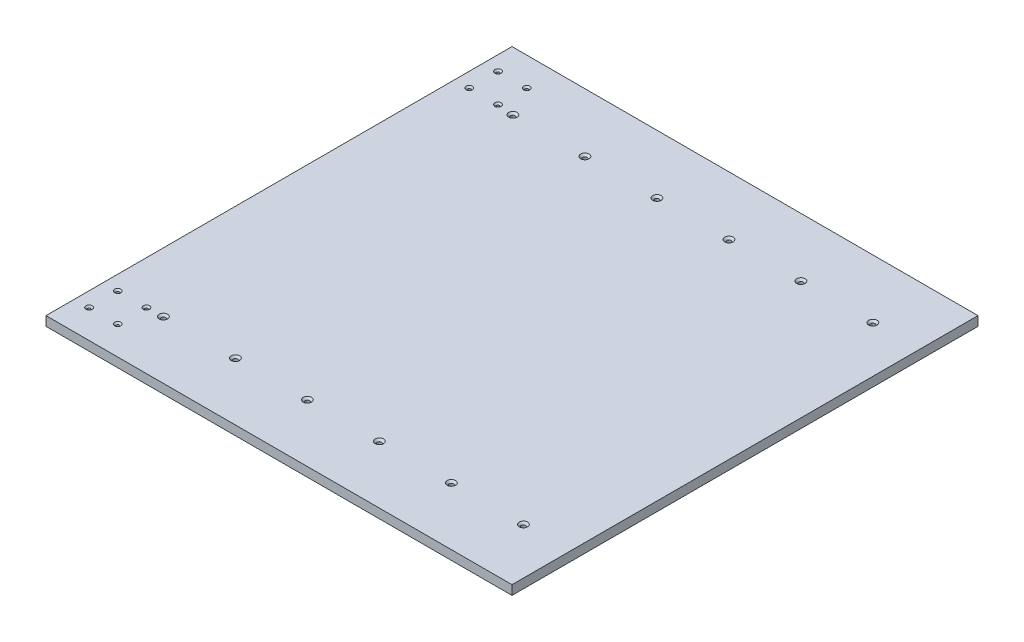
SolidWorks part; units mm, degrees
material "Buk"
ref_plane "Płaszczyzna przednia" through (0, 0, 0) normal (0, 0, 1) x (1, 0, 0)
ref_plane "Płaszczyzna górna" through (0, 0, 0) normal (0, 1, 0) x (1, 0, 0)
ref_plane "Płaszczyzna prawa" through (0, 0, 0) normal (1, 0, 0) x (0, 0, -1)
sketch "Szkic1" plane through (0, 0, 0) normal (0, 1, 0) x (1, 0, 0)
  line L1 (0, 0) -> (500, 0)
  line L2 (0, 0) -> (0, 500)
  line L3 (0, 500) -> (500, 500)
  line L4 (500, 0) -> (500, 500)
  dimension "D1" = 500
extrude "Dodanie-wyciągnięcie1" add sketch "Szkic1" along normal blind 10
sketch "Szkic2" plane through (0, 10, 0) normal (0, 1, 0) x (1, 0, 0)
  line L0 (0, 0) -> (500, 0) construction
  line L1 (0, 500) -> (0, 0) construction
  line L2 (0, 250) -> (500, 250) construction
  line L3 (500, 0) -> (500, 500) construction
  circle A0 centre (15.6, 30.6) radius 1.6
  circle A1 centre (15.6, 61.4) radius 1.6
  circle A2 centre (46.4, 61.4) radius 1.6
  circle A3 centre (46.4, 30.6) radius 1.6
  circle A4 centre (15.6, 438.6) radius 1.6
  circle A5 centre (15.6, 469.4) radius 1.6
  circle A6 centre (46.4, 469.4) radius 1.6
  circle A7 centre (46.4, 438.6) radius 1.6
  dimension "D1" = 3.2
  dimension "D2" = 3.2
  dimension "D3" = 3.2
  dimension "D4" = 3.2
  dimension "D5" = 30.6
  dimension "D6" = 30.6
  dimension "D7" = 30.8
  dimension "D8" = 15.6
  dimension "D9" = 15.6
  dimension "D10" = 30.8
  dimension "D11" = 30.8
  dimension "D12" = 30.8
hole_wizard "Pogłębienie stożkowe pod M3 Wkręt ustalający1" positions "Szkic3" profile "Szkic5" countersink size "M3" standard "Ansi Metric"
sketch "Szkic3" plane through (0, 10, 0) normal (0, 1, 0) x (1, 0, 0)
  point P0 (46.4, 30.6)
  point P3 (46.4, 61.4)
  point P6 (15.6, 61.4)
  point P9 (15.6, 30.6)
  point P12 (46.4, 438.6)
  point P15 (46.4, 469.4)
  point P18 (15.6, 469.4)
  point P21 (15.6, 438.6)
sketch "Szkic5" plane through (46.4, 10, -30.6) normal (1, 0, 0) x (0, 0, 1)
  line L0 (0, 0) -> (0, 11.0215)
  line L1 (0, 11.0215) -> (1.7, 10)
  line L2 (1.7, 10) -> (1.7, 1.66)
  line L3 (1.7, 1.66) -> (3.36, 0)
  line L5 (3.36, 0) -> (0, 0)
  line L6 (-1.7, 1.66) -> (-3.36, 0) construction
  line L10 (0, 11.0215) -> (-1.7, 10) construction
  line L11 (0, -6.35) -> (0, 107.95) construction
  dimension "Œrednica otworu" = 3.4
  dimension "G³êbokoœc otworu" = 10
  dimension "Œrednica zewnêtrznego pog³êbienia sto¿kowego" = 6.72
  dimension "K¹t zewnêtrznego pog³êbienia sto¿kowego" = 90
  dimension "K¹t wiert³a" = 118
hole_wizard "Pogłębienie stożkowe pod M4 Wkręt ustalający1" positions "Szkic6" profile "Szkic7" countersink size "M4" standard "Ansi Metric"
sketch "Szkic6" plane through (0, 10, 0) normal (0, 1, 0) x (1, 0, 0)
  line L0 (0, 500) -> (0, 0) construction
  line L1 (0, 0) -> (500, 0) construction
  point P0 (63.9, 62.07)
  point P14 (141.15, 62.07)
  point P15 (218.4, 62.07)
  point P16 (295.65, 62.07)
  point P17 (372.9, 62.07)
  point P18 (450.15, 62.07)
  point P19 (141.15, 437.07)
  point P20 (218.4, 437.07)
  point P21 (295.65, 437.07)
  point P22 (372.9, 437.07)
  point P23 (450.15, 437.07)
  point P24 (63.9, 437.07)
  dimension "D1" = 63.9
  dimension "D2" = 62.07
  dimension "D3" = 6
  dimension "D4" = 2
sketch "Szkic7" plane through (63.9, 10, -62.07) normal (1, 0, 0) x (0, 0, 1)
  line L0 (0, 0) -> (0, 12.9421)
  line L1 (0, 12.9421) -> (2.4, 11.5)
  line L2 (2.4, 11.5) -> (2.4, 2.08)
  line L3 (2.4, 2.08) -> (4.48, 0)
  line L5 (4.48, 0) -> (0, 0)
  line L6 (-2.4, 2.08) -> (-4.48, 0) construction
  line L10 (0, 12.9421) -> (-2.4, 11.5) construction
  line L11 (0, -6.35) -> (0, 107.95) construction
  dimension "Œrednica otworu" = 4.8
  dimension "G³êbokoœc otworu" = 11.5
  dimension "Œrednica zewnêtrznego pog³êbienia sto¿kowego" = 8.96
  dimension "K¹t zewnêtrznego pog³êbienia sto¿kowego" = 90
  dimension "K¹t wiert³a" = 118
sketch "Szkic8" plane through (0, 0, 0) normal (0, -1, 0) x (1, 0, 0)
  line L0 (0, -500) -> (0, 0) construction
  line L1 (60, -37) -> (460, -37)
  line L2 (60, -37) -> (60, -47)
  line L3 (60, -47) -> (460, -47)
  line L4 (460, -37) -> (460, -47)
  line L5 (0, 0) -> (500, 0) construction
  line L6 (60, -77) -> (60, -87)
  line L7 (60, -77) -> (460, -77)
  line L8 (460, -77) -> (460, -87)
  line L9 (60, -87) -> (460, -87)
  line L10 (60, -452) -> (60, -462)
  line L11 (60, -462) -> (460, -462)
  line L12 (460, -452) -> (460, -462)
  line L13 (60, -452) -> (460, -452)
  line L14 (60, -412) -> (60, -422)
  line L15 (60, -412) -> (460, -412)
  line L16 (460, -412) -> (460, -422)
  line L17 (60, -422) -> (460, -422)
  dimension "D1" = 10
  dimension "D2" = 400
  dimension "D3" = 60
  dimension "D4" = 2
  dimension "37" = 37
  dimension "D5" = 10
  dimension "D6" = 375
extrude "Wytnij-wyciągnięcie1" cut sketch "Szkic8" against normal blind 1
fillet "Zaokrąglenie1" radius 2 16 edges at (460, 1, -457) (260, 1, -462) (60, 1, -457) (260, 1, -452) (460, 1, -417) (260, 1, -422) (60, 1, -417) (260, 1, -412) (460, 1, -82) (260, 1, -87) (60, 1, -82) (260, 1, -77) (260, 1, -37) (460, 1, -42) (260, 1, -47) (60, 1, -42)
